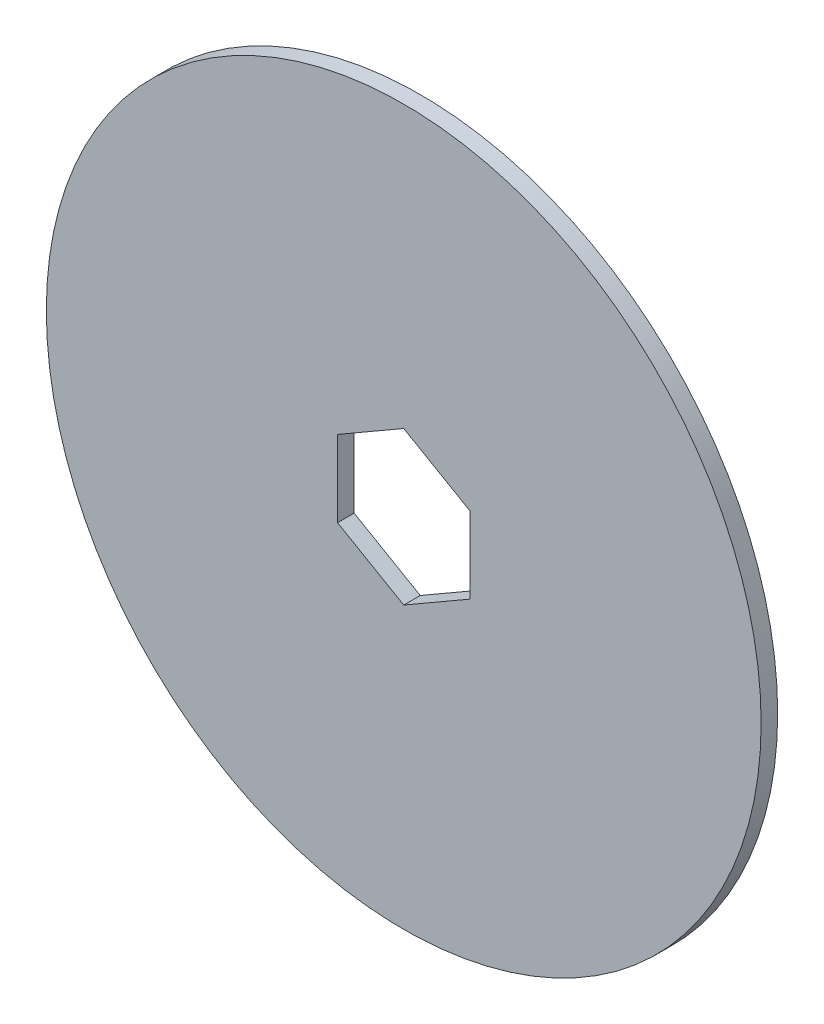
SolidWorks part; units mm, degrees
ref_plane "Front Plane" through (0, 0, 0) normal (0, 0, 1) x (1, 0, 0)
ref_plane "Top Plane" through (0, 0, 0) normal (0, 1, 0) x (1, 0, 0)
ref_plane "Right Plane" through (0, 0, 0) normal (1, 0, 0) x (0, 0, -1)
sketch "Sketch1" plane through (0, 0, 0) normal (0, 0, 1) x (1, 0, 0)
  line L1 (0, 7.3323) -> (-6.35, 3.6662)
  line L2 (-6.35, 3.6662) -> (-6.35, -3.6662)
  line L3 (-6.35, -3.6662) -> (0, -7.3323)
  line L4 (0, -7.3323) -> (6.35, -3.6662)
  line L5 (6.35, -3.6662) -> (6.35, 3.6662)
  line L6 (6.35, 3.6662) -> (0, 7.3323)
  circle A0 centre (0, 0) radius 34.29
  circle A1 centre (0, 0) radius 6.35 construction
  point P3 (0, 0)
  dimension "D1" = 68.58
  dimension "D2" = 12.7
extrude "Boss-Extrude1" add sketch "Sketch1" along normal blind 1.5875
